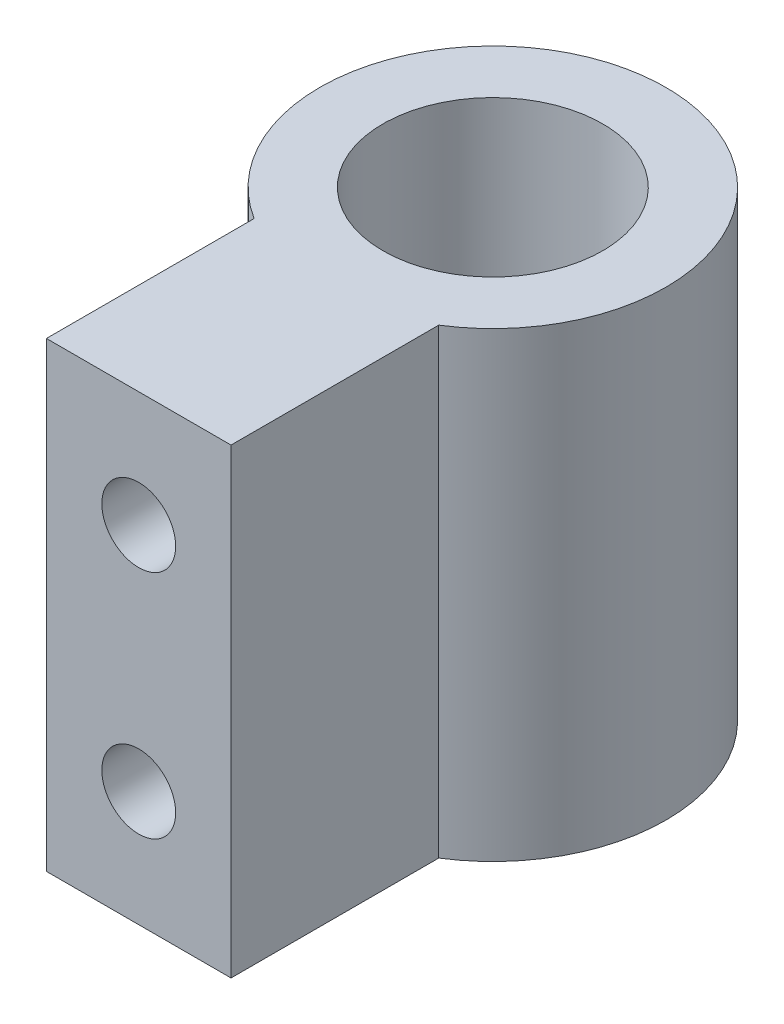
SolidWorks part; units mm, degrees
ref_plane "Front Plane" through (0, 0, 0) normal (0, 0, 1) x (1, 0, 0)
ref_plane "Top Plane" through (0, 0, 0) normal (0, 1, 0) x (1, 0, 0)
ref_plane "Right Plane" through (0, 0, 0) normal (1, 0, 0) x (0, 0, -1)
sketch "Sketch1" plane through (0, 0, 0) normal (0, 1, 0) x (1, 0, 0)
  line L9 (-5.08, -14.4072) -> (5.08, -14.4072)
  line L10 (-5.08, -14.4072) -> (-5.08, -19.4872)
  line L11 (-5.08, -19.4872) -> (5.08, -19.4872)
  line L12 (5.08, -14.4072) -> (5.08, -19.4872)
  line L13 (-5.08, -8.0572) -> (5.08, -8.0572)
  line L14 (-5.08, -8.0572) -> (-5.08, -14.4072)
  line L15 (-5.08, -14.4072) -> (5.08, -14.4072)
  line L16 (5.08, -8.0572) -> (5.08, -14.4072)
  circle A2 centre (0, 0) radius 9.525
  circle A3 centre (0, 0) radius 6.05
  point P3 (0, -9.525)
  dimension "D1" = 12.1
  dimension "D2" = 19.05
  dimension "D3" = 10.16
  dimension "D4" = 6.35
  dimension "D5" = 5.08
extrude "Boss-Extrude1" add sketch "Sketch1" along normal blind 25.4 contours L12 L9 L10 L11 | A2 | A3 A2 | L10 L9 L12 L11 | A2 | A3 region at (0, 0, 11.7121) region at (0, 0, 16.9472) region at (-4.4758, 0, -8.1131)
sketch "Sketch4" plane through (0, 0, 19.4872) normal (0, 0, 1) x (1, 0, 0)
  line L0 (-5.08, 25.4) -> (5.08, 25.4) construction
  circle A0 centre (0, 19.05) radius 2.032
  circle A1 centre (0, 6.35) radius 2.032
  point P7 (0, 25.4)
  dimension "D1" = 4.064
  dimension "D2" = 12.7
  dimension "D3" = 6.35
extrude "Cut-Extrude2" cut sketch "Sketch4" against normal blind 12.7
